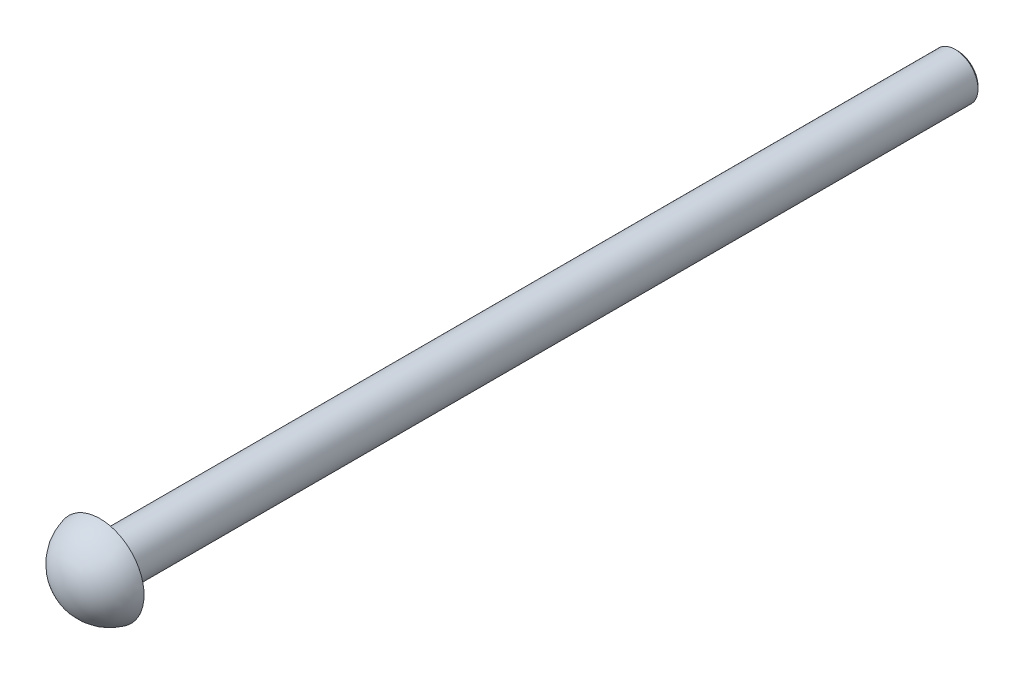
SolidWorks part; units mm, degrees
ref_plane "Front Plane" through (0, 0, 0) normal (0, 0, 1) x (1, 0, 0)
ref_plane "Top Plane" through (0, 0, 0) normal (0, 1, 0) x (1, 0, 0)
ref_plane "Right Plane" through (0, 0, 0) normal (1, 0, 0) x (0, 0, -1)
sketch "Sketch1" plane through (0, 0, 0) normal (0, 0, 1) x (1, 0, 0)
  circle A0 centre (0, 0) radius 1.9325
  dimension "D1" = 3.865
extrude "Boss-Extrude1" add sketch "Sketch1" along normal blind 112.316
cosmetic thread "Cosmetic Thread1" parameters "D1"=6, "D2"=5.693
sketch "Sketch2" plane through (0, 0, 112.316) normal (0, 0, 1) x (1, 0, 0)
  circle A0 centre (0, 0) radius 3.73
extrude "Boss-Extrude2" add sketch "Sketch2" along normal blind 0.001
dome "Dome1" faces to dome 1 distance 3 reverse direction no elliptical dome no face at (3.73, 0, 112.317) parameters "D1"=3
scale "Scale1" scale about centroid uniform scaling yes scale factor 1.5
sketch "Sketch3" plane through (0, 0, -29.7124) normal (0, 0, -1) x (-1, 0, 0)
  circle A1 centre (0, 0) radius 2.8988
  circle A2 centre (0, 0) radius 2.8988
  dimension "D1" = 0
extrude "Cut-Extrude1" cut sketch "Sketch3" against normal blind 59.7
chamfer "Chamfer1" distance 0.3 angle 45 1 edges at (-2.8988, 0, 29.9876)
